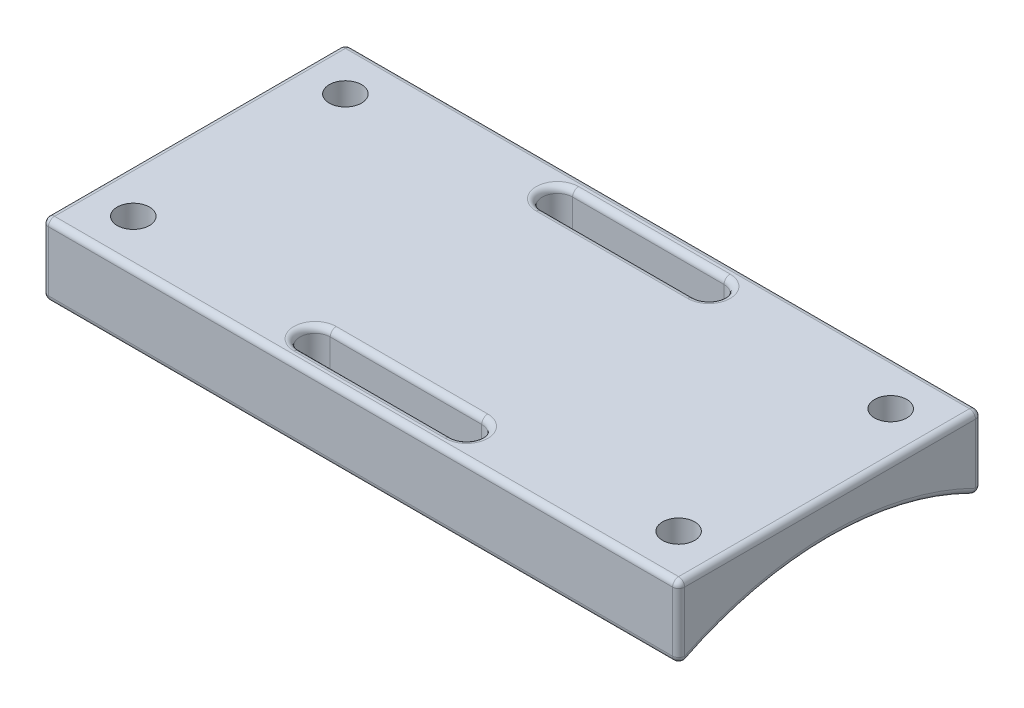
SolidWorks part; units mm, degrees
ref_plane "Front Plane" through (0, 0, 0) normal (0, 0, 1) x (1, 0, 0)
ref_plane "Top Plane" through (0, 0, 0) normal (0, 1, 0) x (1, 0, 0)
ref_plane "Right Plane" through (0, 0, 0) normal (1, 0, 0) x (0, 0, -1)
sketch "Sketch1" plane through (0, 0, 0) normal (0, 1, 0) x (1, 0, 0)
  line L1 (0, 0) -> (53.34, 0)
  line L2 (0, 0) -> (0, 25.4)
  line L3 (0, 25.4) -> (53.34, 25.4)
  line L4 (53.34, 0) -> (53.34, 25.4)
  dimension "D1" = 53.34
  dimension "D2" = 25.4
extrude "Boss-Extrude1" add sketch "Sketch1" along normal blind 6.35
sketch "Sketch3" plane through (0, 6.35, 0) normal (0, 1, 0) x (1, 0, 0)
  line L0 (0, 25.4) -> (0, 0) construction
  line L1 (53.34, 25.4) -> (0, 25.4) construction
  line L2 (53.34, 0) -> (53.34, 25.4) construction
  line L3 (0, 0) -> (53.34, 0) construction
  point P0 (3.81, 21.59)
  point P1 (49.53, 21.59)
  point P2 (3.81, 3.81)
  point P3 (49.53, 3.81)
  dimension "D1" = 3.81
  dimension "D2" = 3.81
  dimension "D3" = 3.81
  dimension "D4" = 3.81
  dimension "D5" = 3.81
  dimension "D6" = 3.81
  dimension "D7" = 3.81
  dimension "D8" = 3.81
ref_plane "Plane1" through (0, 0, 0) normal (0, 1, 0) x (1, 0, 0)
sketch "Sketch6" plane through (0, 0, 0) normal (0, 1, 0) x (1, 0, 0)
  point P0 (3.81, 21.59)
  point P2 (49.53, 21.59)
  point P4 (49.53, 3.81)
  point P6 (3.81, 3.81)
hole_wizard "CBORE for M2.5 SHCS1" positions "Sketch7" profile "Sketch8" counterbore size "M2.5" standard "ANSI Metric" end condition through all
sketch "Sketch7" plane through (0, 0, 0) normal (0, 1, 0) x (1, 0, 0)
  point P0 (3.81, 3.81)
  point P3 (3.81, 21.59)
  point P6 (49.53, 3.81)
  point P9 (49.53, 21.59)
sketch "Sketch8" plane through (3.81, 0, -3.81) normal (1, 0, 0) x (0, 0, -1)
  line L0 (0, 0) -> (0, 6.35)
  line L1 (0, 6.35) -> (1.35, 6.35)
  line L3 (1.35, 6.35) -> (1.35, 3.175)
  line L4 (1.35, 3.175) -> (3.25, 3.175)
  line L5 (3.25, 3.175) -> (3.25, 0)
  line L7 (3.25, 0) -> (0, 0)
  line L11 (0, -6.35) -> (0, 107.95) construction
  dimension "Thru Hole Dia." = 2.7
  dimension "Thru Hole Depth" = 6.35
  dimension "C'Bore Dia." = 6.5
  dimension "C'Bore Depth" = 3.175
sketch "Sketch9" plane through (0, 6.35, 0) normal (0, 1, 0) x (1, 0, 0)
  line L0 (0, 25.4) -> (0, 0) construction
  line L1 (20.32, 3.81) -> (33.02, 3.81)
  line L3 (20.32, 1.27) -> (33.02, 1.27)
  line L5 (0, 0) -> (53.34, 0) construction
  line L6 (0, 12.7) -> (4.9341, 12.7) construction
  line L9 (20.32, 24.13) -> (33.02, 24.13)
  line L10 (20.32, 21.59) -> (33.02, 21.59)
  arc A0 (33.02, 1.27) -> (33.02, 3.81) centre (33.02, 2.54) ccw
  arc A1 (20.32, 3.81) -> (20.32, 1.27) centre (20.32, 2.54) ccw
  arc A4 (20.32, 21.59) -> (20.32, 24.13) centre (20.32, 22.86) cw
  arc A5 (33.02, 24.13) -> (33.02, 21.59) centre (33.02, 22.86) cw
  point P18 (20.1362, 2.54)
  dimension "D2" = 20.32
  dimension "D1" = 12.7
  dimension "D3" = 1.27
  dimension "D4" = 2.54
extrude "Cut-Extrude2" cut sketch "Sketch9" against normal blind 67.818
sketch "Sketch10" plane through (53.34, 0, 0) normal (1, 0, 0) x (0, 0, -1)
  line L0 (12.7, 0) -> (12.7, 4.1153) construction
  line L4 (0, 0) -> (25.4, 0)
  line L5 (25.4, 0) -> (25.4, 6.35)
  line L6 (25.4, 6.35) -> (0, 6.35)
  line L7 (0, 6.35) -> (0, 0)
  line L8 (0, 0) -> (25.4, 0)
  line L9 (25.4, 0) -> (25.4, 6.35)
  line L10 (25.4, 6.35) -> (0, 6.35)
  line L11 (0, 6.35) -> (0, 0)
  arc A0 (0, 0) -> (25.4, 0) centre (12.7, -23.8125) cw
  point P7 (12.7, 3.175)
  line M6 (0, 0) -> (25.4, 0)
  dimension "D2" = 3.175
  dimension "D1" = 0
extrude "Cut-Extrude3" cut sketch "Sketch10" against normal blind 482.346 contours L0 A0 M6 | L0 L8 A0 region at (53.34, 1.2766, -7.8978) region at (53.34, 1.2766, -17.5022)
fillet "Fillet3" radius 0.508 28 edges at (19.0523, 1.1586, -2.4644) (26.67, 1.6687, -3.81) (34.2885, 1.2149, -2.6027) (19.0515, 1.2149, -22.7973) (26.67, 0.635, -24.13) (34.2877, 1.1586, -22.9356) (34.29, 6.35, -2.54) (26.67, 6.35, -1.27) (19.05, 6.35, -2.54) (19.05, 6.35, -22.86) (26.67, 6.35, -24.13) (34.29, 6.35, -22.86) (0, 3.175, -25.4) (0, 6.35, -12.7) (0, 3.175, 0) (0, 3.175, -12.7) (26.67, 0.635, -1.27) (26.67, 1.6687, -21.59) (26.67, 0, -25.4) (53.34, 3.175, -12.7) (53.34, 3.175, -25.4) (53.34, 3.175, 0) (26.67, 0, 0) (26.67, 6.35, -3.81) (26.67, 6.35, -21.59) (53.34, 6.35, -12.7) (26.67, 6.35, -25.4) (26.67, 6.35, 0)
